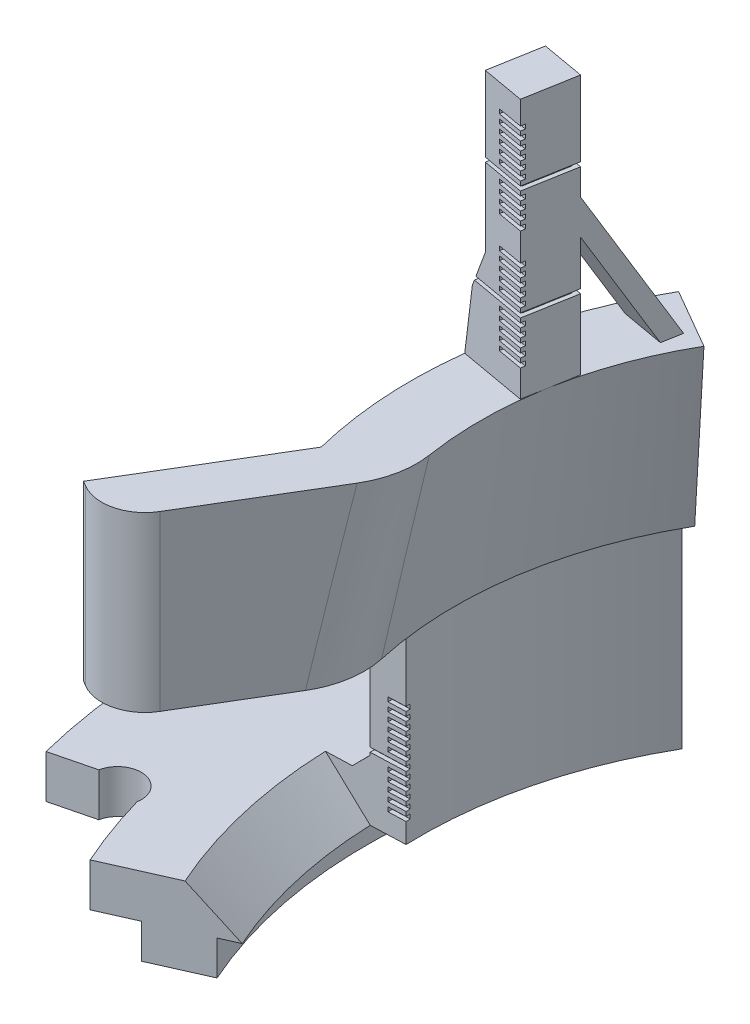
SolidWorks part; units mm, degrees
note: The reader was unsure of these and kept them because the rebuilt part matched: shared geometry of "Sketch9<2>".
ref_plane "Front Plane" through (0, 0, 0) normal (0, 0, 1) x (1, 0, 0)
ref_plane "Top Plane" through (0, 0, 0) normal (0, 1, 0) x (1, 0, 0)
ref_plane "Right Plane" through (0, 0, 0) normal (1, 0, 0) x (0, 0, -1)
sketch "Sketch1" plane through (0, 0, 0) normal (0, 0, 1) x (1, 0, 0)
  line L1 (-5, 10) -> (5, 10)
  line L2 (-5, 10) -> (-5, 0)
  line L3 (-5, 0) -> (5, 0)
  line L4 (5, 10) -> (5, 0)
  dimension "D1" = 10
  dimension "D2" = 10
extrude "Boss-Extrude1" [suppressed] add sketch "Sketch1" against normal blind 10 draft 15 contours L4 L3 L2 L1
sketch "Sketch2" plane through (0, 0, 0) normal (0, 0, 1) x (1, 0, 0)
  line L0 (0, 0) -> (0, 29.4965) construction
sketch "Sketch3" plane through (0, 0, 0) normal (0, 1, 0) x (1, 0, 0)
  circle A0 centre (0, 0) radius 45 construction
  dimension "D1" = 90
sketch "Sketch7" plane through (0, 0, 0) normal (0, 0, 1) x (1, 0, 0)
  line L0 (-75, 8) -> (-60.5, 8)
  line L1 (-60.5, 8) -> (-60.5, 4)
  line L2 (-60.5, 4) -> (-53.9, 4)
  line L3 (-53.9, 4) -> (-53.9, 8)
  line L4 (-53.9, 8) -> (-47.7, 8)
  line L5 (-47.7, 8) -> (-47.7, 18)
  line L6 (-47.7, 18) -> (-47.7, 33)
  line L8 (-40.7823, 53) -> (-48.7823, 53)
  line L10 (-51.7, 13) -> (-75, 13)
  line L11 (-75, 13) -> (-75, 8)
  line L12 (0, -200000) -> (0, 200029.4965) construction
  line L13 (-47.7, 33) -> (-43.7, 33)
  line L14 (-43.7, 33) -> (-40.7823, 53)
  line L15 (-48.7823, 53) -> (-51.7, 33)
  line L16 (-51.7, 33) -> (-51.7, 13)
  dimension "D1" = 53.9
  dimension "D2" = 6.6
  dimension "D3" = 4
  dimension "D4" = 4
  dimension "D5" = 75
  dimension "D6" = 5
  dimension "D7" = 6.2
  dimension "D8" = 90
  dimension "D9" = 10
  dimension "D10" = 15
  dimension "D11" = 20
  dimension "D12" = 98.3
  dimension "D13" = 4
  dimension "D14" = 4
  dimension "D15" = 98.3
revolve "back" add sketch "Sketch7" angle 14 about L0
sketch "Sketch9" plane through (0, 8, 0) normal (0, -1, 0) x (-1, 0, 0)
  line L0 (0, 0) -> (65.2, 17.4703) construction
  line L1 (65.2, 17.4703) -> (65.2, 14.7203) construction
  line L2 (65.2, -17.4703) -> (0, 0) construction
  line L3 (65.2, -14.7203) -> (65.2, -17.4703) construction
  line L4 (83.6224, 0) -> (170.0314, 0) construction
  circle A0 centre (65.2, 17.4703) radius 2.75
  circle A1 centre (65.2, -17.4703) radius 2.75
  dimension "D1" = 5.5
  dimension "D2" = 5.5
  dimension "D3" = 67.5
  dimension "D4" = 67.5
  dimension "D5" = 15
sketch "Sketch10" plane through (0, 0, 0) normal (0, 0, 1) x (1, 0, 0)
  line L0 (-40.7823, 53) -> (-39.3235, 63)
  line L1 (-39.3235, 63) -> (-46.3235, 63)
  line L2 (-46.3235, 63) -> (-47.7823, 53)
  line L4 (-39.5709, 53) -> (-47.3333, 53) construction
  line L5 (-47.7823, 53) -> (-40.7823, 53)
  dimension "D1" = 7
  dimension "D2" = 98.3
  dimension "D3" = 10
revolve "top ruler" [suppressed] add sketch "Sketch10" angle 5 about L0
extrude "screw hole" cut sketch "Sketch9" against normal through all
sketch "Sketch11" plane through (0, 53, 0) normal (0, 1, 0) x (1, 0, 0)
  line L0 (-47.3333, -11.8015) -> (-39.5709, -9.8661)
  line L1 (-39.5709, -9.8661) -> (-52.7852, -31.8584)
  line L2 (-52.7852, -31.8584) -> (-57.634, -28.9449)
  line L3 (-57.634, -28.9449) -> (-47.3333, -11.8015)
  dimension "D1" = 45
  dimension "D2" = 20
extrude "Boss-Extrude2" add sketch "Sketch11" against normal up to surface (20 mm away) up to face at (-43.6076, 33, -6.1286)
sketch "Sketch12" plane through (0, 0, 0) normal (-0.2419, 0, -0.9703) x (-0.9703, 0, 0.2419)
  line L3 (40.7823, 33) -> (43.7, 33)
  line L4 (43.7, 33) -> (40.7823, 53)
  line L5 (40.7823, 53) -> (40.7823, 33)
  line L6 (40.7823, 33) -> (43.7, 33)
  line L7 (43.7, 33) -> (40.7823, 53)
  line L8 (40.7823, 53) -> (40.7823, 33)
  dimension "D1" = 0
extrude "Cut-Extrude1" cut sketch "Sketch12" against normal blind 10
fillet "Fillet1" radius 10 1 edges at (-40.6335, 43, 11.6346)
fillet "Fillet2" radius 5 1 edges at (-52.7852, 43, 31.8584)
sketch "Sketch13" [suppressed] plane through (0, 0, 0) normal (0, 0, 1) x (1, 0, 0)
  line L0 (-40.8823, 53) -> (-42.3412, 43)
  line L1 (-42.3412, 43) -> (-39.3412, 43)
  line L2 (-39.3412, 43) -> (-37.8823, 53)
  line L3 (-37.8823, 53) -> (-40.8823, 53)
  line L4 (-61.4524, 53) -> (-61.0576, 53) construction
  dimension "D1" = 98.3
  dimension "D2" = 0.1
  dimension "D3" = 3
  dimension "D4" = 10
sketch "Sketch14" plane through (0, 53, 0) normal (0, 1, 0) x (1, 0, 0)
  line L0 (-40.0976, 7.4419) -> (0.0861, 0.3247) construction
  line L1 (-39.5744, 10.396) -> (-40.6208, 4.4879)
  line L2 (-40.6208, 4.4879) -> (-45.5441, 5.3599)
  line L3 (-45.5441, 5.3599) -> (-44.4977, 11.268)
  line L4 (-44.4977, 11.268) -> (-39.5744, 10.396)
  arc A0 (-35.3185, 20.3912) -> (-40.2834, -6.3597) centre (0, 0) ccw construction
  dimension "D1" = 5
  dimension "D2" = 6
extrude "Boss-Extrude3" add sketch "Sketch14" along normal blind 30
chamfer "Chamfer1" distance 5 angle 67 1 edges at (-45.0209, 53, -8.314)
sketch "Sketch15" plane through (-0.4648, 0, 2.6244) normal (-0.1744, 0, 0.9847) x (0.9847, 0, 0.1744)
  line L0 (-40.7809, 61.1207) -> (-50.7809, 61.1207)
  line L1 (-40.7809, 83) -> (-40.7809, 53) construction
  line L2 (-40.7809, 73.8207) -> (-45.7809, 73.8207)
  line L3 (26.5382, 73.8207) -> (-26.4818, 73.8207) construction
  line L4 (39.4219, 61.1207) -> (-39.3655, 61.1207) construction
  dimension "D1" = 10
  dimension "D2" = 5
sketch "Sketch20" plane through (-40.1559, 0, -7.1123) normal (0.9847, 0, 0.1744) x (0.1744, 0, -0.9847)
  line L0 (-2.6652, 61.1207) -> (3.3348, 61.1207)
  line L1 (3.3348, 83) -> (3.3348, 53) construction
  line L2 (-2.6652, 73.8207) -> (3.3348, 73.8207)
sketch "Sketch21" plane through (0.5816, 0, -3.2837) normal (0.1744, 0, -0.9847) x (-0.9847, 0, -0.1744)
  line L0 (40.7809, 61.1207) -> (50.3061, 61.1207)
  line L1 (40.7809, 73.8207) -> (45.7809, 73.8207)
  line L3 (45.7809, 83) -> (45.7809, 64.7793) construction
extrude "Cut-Extrude-Thin2" cut sketch "Sketch21" against normal blind 0.5 thin thin type one direction reverse wall 0.5
extrude "up long" cut sketch "Sketch15" against normal blind 0.5 thin
extrude "Cut-Extrude-Thin4" cut sketch "Sketch20" against normal blind 0.5 thin thin type one direction reverse wall 0.5
sketch "Sketch22" plane through (-0.4648, 0, 2.6244) normal (-0.1744, 0, 0.9847) x (0.9847, 0, 0.1744)
  line L0 (-40.7809, 74.8207) -> (-43.7809, 74.8207)
  line L1 (-40.7809, 83) -> (-40.7809, 74.3207) construction
  line L2 (-40.7809, 73.8207) -> (-45.7809, 73.8207) construction
  dimension "D1" = 1
  dimension "2" = 3
extrude "short" cut sketch "Sketch22" against normal blind 0.5 thin
pattern_linear "LPattern1" count 6 spacing 1 along (0, 1, 0) of "short"
pattern_linear "LPattern3" count 6 spacing 1 along (0, -1, 0) of "short"
sketch "Sketch23" plane through (-0.4648, 0, 2.6244) normal (-0.1744, 0, 0.9847) x (0.9847, 0, 0.1744)
  line L0 (-40.7809, 62.1207) -> (-43.7809, 62.1207)
  line L1 (-40.7809, 69.8207) -> (-40.7809, 61.6207) construction
  line L2 (-40.7809, 61.1207) -> (-47.3339, 61.1207) construction
  dimension "D1" = 3
  dimension "D2" = 1
extrude "short 2" cut sketch "Sketch23" against normal blind 0.5 thin
pattern_linear "LPattern4" count 5 spacing 1 along (0, 1, 0) of "short 2"
pattern_linear "LPattern5" count 7 spacing 1 along (0, -1, 0) of "short 2"
sketch "Sketch24" plane through (0, 0, 0) normal (0.2419, 0, 0.9703) x (0.9703, 0, -0.2419)
  line L0 (-47.7, 14.5737) -> (-51.7, 14.5737)
  line L1 (-47.7, 8) -> (-47.7, 33) construction
  line L2 (-51.7, 33) -> (-51.7, 13) construction
  line L3 (-46.0191, 14.5737) -> (11.1112, 14.5737) construction
extrude "Cut-Extrude-Thin7" [suppressed] cut sketch "Sketch24" against normal blind 0.1 thin
sketch "Sketch25" [suppressed] plane through (0, 0, 0) normal (0.2079, 0, 0.9781) x (0.9781, 0, -0.2079)
  line L0 (-47.7, 15.5737) -> (-50.2, 15.5737)
  line L1 (-47.7, 15.0737) -> (-47.7, 33) construction
  line L2 (-47.7, 14.5737) -> (-51.7, 14.5737) construction
  dimension "D1" = 2.5
  dimension "D2" = 1
extrude "Cut-Extrude-Thin8" [suppressed] cut sketch "Sketch25" against normal blind 0.1 thin
pattern_linear "LPattern6" [suppressed] count 6 spacing 1
pattern_linear "LPattern8" [suppressed] count 6 spacing 1
mirror "Mirror2" [suppressed] about plane through (0, 0, 0) normal (1, 0, 0)
sketch "Sketch26" plane through (0, 0, 0) normal (0, 1, 0) x (1, 0, 0)
  line L1 (-86.7378, 103.6026) -> (-21.8376, 103.6026)
  line L2 (-86.7378, 103.6026) -> (-86.7378, -74.3667)
  line L3 (-86.7378, -74.3667) -> (-21.8376, -74.3667)
  line L4 (-21.8376, 103.6026) -> (-21.8376, -74.3667)
extrude "Cut-Extrude3" [suppressed] cut sketch "Sketch26" along normal through all
sketch "Sketch27" plane through (0, 0, 0) normal (0.2419, 0, 0.9703) x (0.9703, 0, -0.2419)
  line L1 (-51.7, 33) -> (-47.7, 33)
  line L2 (-51.7, 33) -> (-51.7, 8)
  line L3 (-51.7, 8) -> (-47.7, 8)
  line L4 (-47.7, 33) -> (-47.7, 8)
revolve "Cut-Revolve1" cut sketch "Sketch27" angle 12 about L0
sketch "Sketch28" plane through (0, 0, 0) normal (0.2419, 0, 0.9703) x (0.9703, 0, -0.2419)
  line L8 (-51.7, 8) -> (-51.7, 13)
  line L9 (-51.7, 13) -> (-65.0048, 13)
  line L10 (-65.0048, 13) -> (-65.0048, 8)
  line L11 (-65.0048, 13) -> (-65.0048, 8)
  line L12 (-60.5, 8) -> (-60.5, 4)
  line L13 (-60.5, 4) -> (-53.9, 4)
  line L14 (-53.9, 4) -> (-53.9, 8)
  line L15 (-53.9, 8) -> (-51.7, 8)
  line L16 (-51.7, 8) -> (-51.7, 13)
  line L17 (-51.7, 13) -> (-65.0048, 13)
  line L20 (-60.5, 8) -> (-60.5, 4)
  line L21 (-60.5, 4) -> (-53.9, 4)
  line L22 (-53.9, 4) -> (-53.9, 8)
  line L23 (-53.9, 8) -> (-51.7, 8)
  line L24 (-65.0048, 8) -> (-60.5, 8)
  line L25 (-65.0048, 8) -> (-60.5, 8)
  dimension "D1" = 0
revolve "Revolve1" add sketch "Sketch28" angle 10 about L0
extrude "Cut-Extrude4" cut sketch "Sketch9<2>" against normal through all contours A1
sketch "Sketch9<2>" plane through (0, 8, 0) normal (0, -1, 0) x (-1, 0, 0) same geometry as "Sketch9"
chamfer "Chamfer2" distance 5 angle 45 1 edges at (-50.3749, 13, 11.63)
chamfer "Chamfer3" distance 2 angle 45 1 edges at (-50.1643, 13, -12.5074)
ref_plane "Plane1" through (-44.5849, 73.8207, -10.7756) normal (0.1744, 0, -0.9847) x (-0.9847, 0, -0.1744)
sketch "Sketch32" plane through (-45.0793, 0, -7.9843) normal (-0.9847, 0, -0.1744) x (-0.1744, 0, 0.9847)
  line L0 (-3.3348, 66.7793) -> (-11.2902, 53)
  line L1 (-3.3348, 73.8207) -> (-3.3348, 64.7793) construction
  line L2 (-3.3348, 53) -> (-16.6494, 53) construction
  line L3 (-11.2902, 53) -> (-13.5996, 53)
  line L4 (-3.3348, 66.7793) -> (-3.3348, 70.7793)
  line L5 (-3.3348, 70.7793) -> (-13.5996, 53)
  line L6 (-3.3348, 61.6207) -> (-3.3348, 64.7793) construction
  dimension "D1" = 2
  dimension "D2" = 30
  dimension "D3" = 2
extrude "trig support" add sketch "Sketch32" against normal up to surface (5 mm away) up to face at (-40.5292, 67.5857, -5.0049)
sketch "Sketch33" plane through (0, 0, 0) normal (0.0349, 0, 0.9994) x (0.9994, 0, -0.0349)
  line L0 (-47.2487, 15.3089) -> (-51.7, 15.3089)
  line L2 (-51.7, 33) -> (-51.7, 15) construction
  line L4 (46.2787, 15.3089) -> (-46.0838, 15.3089) construction
extrude "long lower" cut sketch "Sketch33" against normal blind 0.5 thin contours L0
sketch "Sketch34" plane through (0, 0, 0) normal (0.0349, 0, 0.9994) x (0.9994, 0, -0.0349)
  line L0 (-49.7, 16.3089) -> (-46.0179, 16.3089)
  line L2 (-47.7, 15.3089) -> (-51.7, 15.3089) construction
  line L3 (-47.7, 15.8089) -> (-47.7, 33) construction
  dimension "D1" = 1
  dimension "D2" = 2
extrude "short  lower" cut sketch "Sketch34" against normal blind 0.5 thin thin type one direction reverse wall 0.5
pattern_linear "LPattern9" count 6 spacing 1 along (0, 1, 0) count 7 spacing 1 along (0, -1, 0) of "short  lower"
